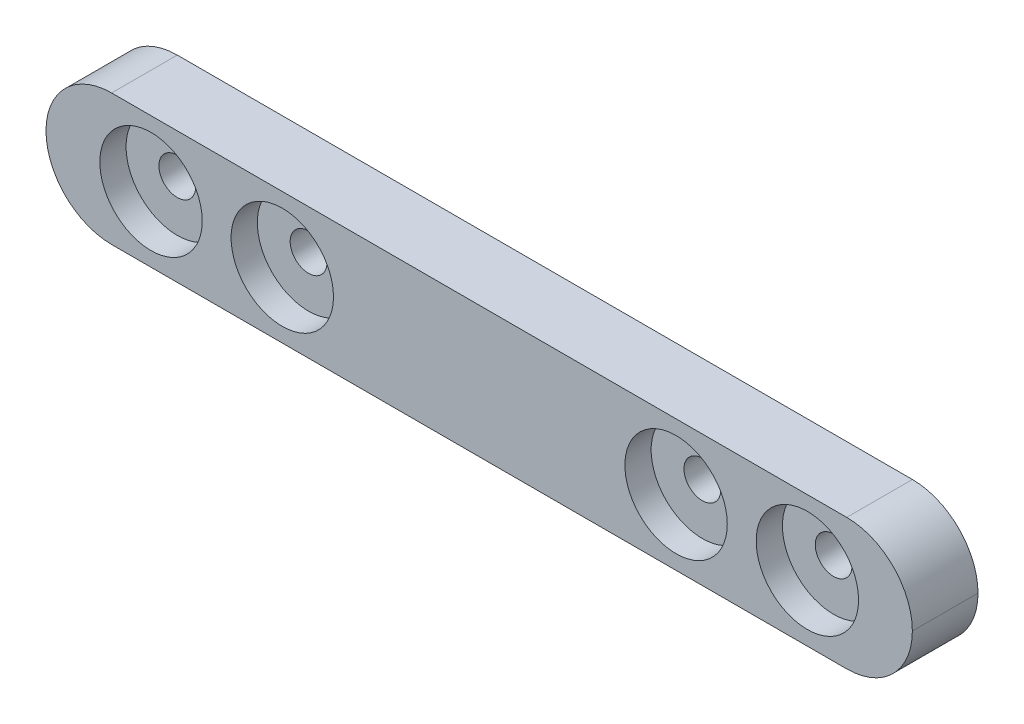
SolidWorks part; units mm, degrees
ref_plane "Front Plane" through (0, 0, 0) normal (0, 0, 1) x (1, 0, 0)
ref_plane "Top Plane" through (0, 0, 0) normal (0, 1, 0) x (1, 0, 0)
ref_plane "Right Plane" through (0, 0, 0) normal (1, 0, 0) x (0, 0, -1)
sketch "Sketch1" plane through (0, 0, 0) normal (0, 1, 0) x (1, 0, 0)
  line L1 (-33, -36) -> (33, -36)
  line L2 (-33, -36) -> (-33, 36)
  line L3 (-33, 36) -> (33, 36)
  line L4 (33, -36) -> (33, 36)
  line L5 (-33, -36) -> (33, 36) construction
  line L6 (-33, 36) -> (33, -36) construction
  point P0 (0, 0)
  dimension "D1" = 72
  dimension "D2" = 66
extrude "Boss-Extrude1" add sketch "Sketch1" along normal blind 10
sketch "Sketch2" plane through (0, 0, 36) normal (0, 0, 1) x (1, 0, 0)
  line L0 (-15, 5) -> (-25, 5) construction
  line L1 (25.4779, 5.6572) -> (25, 5) construction
  line L2 (25, 5) -> (15, 5) construction
  line L3 (-25, 5) -> (25, 5) construction
  line L4 (-33, 0) -> (33, 0) construction
  circle A0 centre (-15, 5) radius 1.4
  circle A1 centre (15, 5) radius 1.4
  circle A3 centre (-25, 5) radius 1.4
  circle A4 centre (25, 5) radius 1.4
  point P9 (0, 5)
  dimension "D1" = 2.8
  dimension "D2" = 50
  dimension "D3" = 10
  dimension "D4" = 5
extrude "Cut-Extrude1" cut sketch "Sketch2" against normal blind 10
mirror "Mirror1" about plane through (0, 0, 0) normal (0, 0, 1) of "Cut-Extrude1"
sketch "Sketch3" plane through (0, 10, 0) normal (0, 1, 0) x (1, 0, 0)
  line L0 (0, 19) -> (0, 0) construction
  line L1 (-15, -21.5) -> (15, -21.5)
  line L2 (-15, -21.5) -> (-15, -16.5)
  line L3 (-15, -16.5) -> (15, -16.5)
  line L4 (15, -21.5) -> (15, -16.5)
  line L5 (-15, -21.5) -> (15, -16.5) construction
  line L6 (-15, -16.5) -> (15, -21.5) construction
  line L7 (-15, 16.5) -> (15, 16.5)
  line L8 (-15, 16.5) -> (-15, 21.5)
  line L9 (-15, 21.5) -> (15, 21.5)
  line L10 (15, 16.5) -> (15, 21.5)
  line L11 (-15, 16.5) -> (15, 21.5) construction
  line L12 (-15, 21.5) -> (15, 16.5) construction
  line L13 (0, 0) -> (0, -19) construction
  point P0 (0, -19)
  point P5 (0, 19)
  dimension "D1" = 5
  dimension "D2" = 30
  dimension "D5" = 19
extrude "Cut-Extrude2" cut sketch "Sketch3" against normal through all both
sketch "Sketch4" plane through (0, 0, 36) normal (0, 0, 1) x (1, 0, 0)
  line L0 (-15, 5) -> (15, 5) construction
  circle A0 centre (0, 5) radius 3.15
  dimension "D1" = 6.3
extrude "Cut-Extrude3" [suppressed] cut sketch "Sketch4" against normal through all both
sketch "Sketch5" plane through (0, 10, 0) normal (0, 1, 0) x (1, 0, 0)
  circle A0 centre (0, 0) radius 7.5
  dimension "D1" = 15
extrude "Boss-Extrude2" add sketch "Sketch5" along normal blind 1.5
sketch "Sketch6" plane through (33, 0, 0) normal (1, 0, 0) x (0, 0, -1)
  line L0 (-36, 10) -> (-36, 0) construction
  line L1 (36, 0) -> (-31, 0)
  line L2 (36, 0) -> (36, 25)
  line L3 (36, 25) -> (-31, 25)
  line L4 (-31, 0) -> (-31, 25)
  dimension "D1" = 5
  dimension "D2" = 25
extrude "Cut-Extrude4" cut sketch "Sketch6" against normal through all
fillet "Fillet1" radius 5 4 edges at (33, 0, 33.5) (33, 10, 33.5) (-33, 0, 33.5) (-33, 10, 33.5)
sketch "Sketch7" plane through (0, 0, 36) normal (0, 0, 1) x (1, 0, 0)
  circle A0 centre (25, 5) radius 1.4 construction
  circle A1 centre (15, 5) radius 1.4 construction
  circle A2 centre (-15, 5) radius 1.4 construction
  circle A3 centre (-25, 5) radius 1.4 construction
  circle A4 centre (25, 5) radius 1.4
  circle A5 centre (15, 5) radius 1.4
  circle A6 centre (-15, 5) radius 1.4
  circle A7 centre (-25, 5) radius 1.4
  circle A8 centre (-25, 5) radius 3.9
  circle A9 centre (-15, 5) radius 3.9
  circle A10 centre (15, 5) radius 3.9
  circle A11 centre (25, 5) radius 3.9
  dimension "D1" = 2.5
extrude "Cut-Extrude5" cut sketch "Sketch7" against normal blind 2
